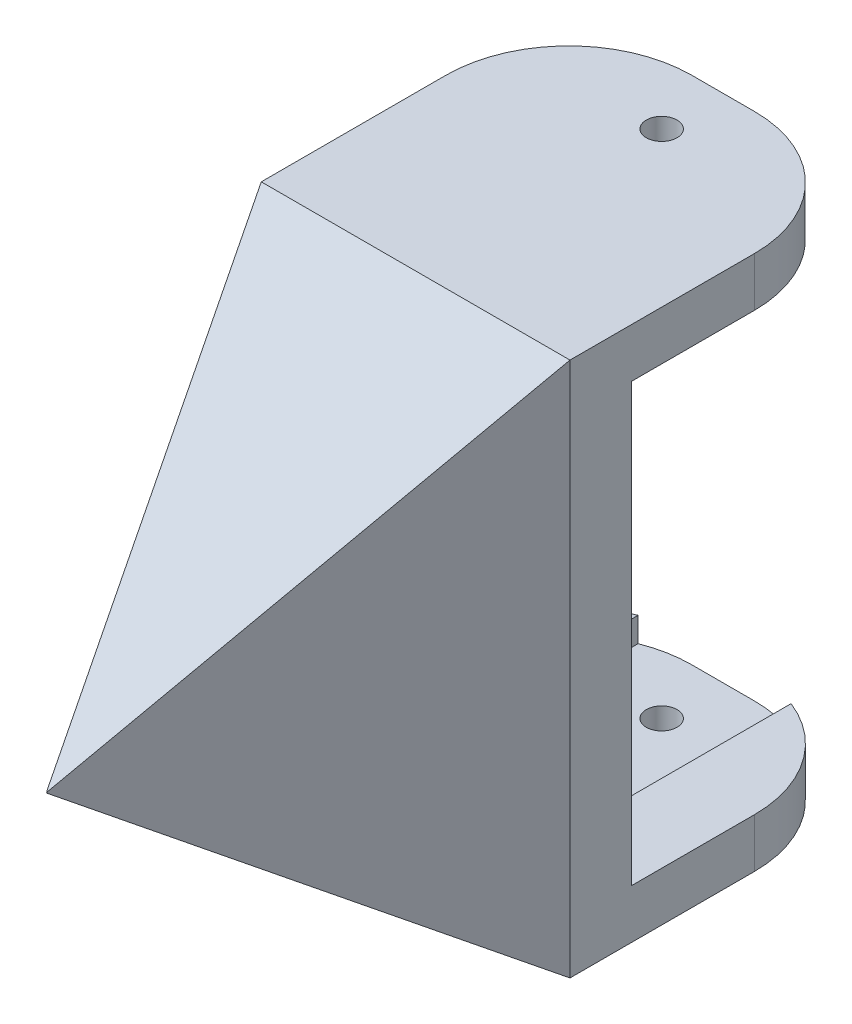
SolidWorks part; units mm, degrees
ref_plane "Front Plane" through (0, 0, 0) normal (0, 0, 1) x (1, 0, 0)
ref_plane "Top Plane" through (0, 0, 0) normal (0, 1, 0) x (1, 0, 0)
ref_plane "Right Plane" through (0, 0, 0) normal (1, 0, 0) x (0, 0, -1)
sketch "Sketch4" plane through (0, 0, 0) normal (0, 0, 1) x (1, 0, 0)
  line L1 (-6.23, -9.975) -> (6.23, -9.975)
  line L2 (-6.23, -9.975) -> (-6.23, 7.275)
  line L3 (-6.23, 7.275) -> (6.23, 7.275)
  line L4 (6.23, -9.975) -> (6.23, 7.275)
  point P4 (0, 7.275)
  dimension "D1" = 12.46
  dimension "D2" = 17.25
  dimension "D3" = 9.975
extrude "Boss-Extrude3" add sketch "Sketch4" along normal blind 6
sketch "Sketch8" plane through (0, -9.975, 0) normal (0, -1, 0) x (-1, 0, 0)
  circle A0 centre (0, -23.55) radius 12.5468
  circle A1 centre (0, -23.55) radius 11.15
  dimension "D1" = 22.3
  dimension "D2" = 23.55
extrude "Boss-Extrude6" add sketch "Sketch8" along normal blind 7.3 and the other way up to surface (17.25 mm away) other way up to face at (0, 7.275, 3)
sketch "Sketch5" plane through (0, 7.275, 0) normal (0, 1, 0) x (1, 0, 0)
  line L8 (12.5468, -23.55) -> (12.5468, 0)
  line L9 (12.5468, 0) -> (6.23, 0)
  line L10 (-12.5468, -23.55) -> (-12.5468, 0)
  line L11 (-12.5468, 0) -> (-6.23, 0)
  line L12 (-6.23, 0) -> (-6.23, -29.7)
  line L14 (6.23, -29.7) -> (6.23, 0)
  line L15 (-6.23, -29.7) -> (6.23, -29.7)
  line L16 (6.23, -6) -> (-6.23, -6) construction
  circle A0 centre (0, -23.55) radius 12.5468 construction
  arc A1 (-12.5468, -23.55) -> (12.5468, -23.55) centre (0, -23.55) ccw
  dimension "D1" = 23.7
  dimension "D2" = 23.55
extrude "Boss-Extrude4" add sketch "Sketch5" against normal up to surface (17.25 mm away) up to face at (0, -9.975, 3)
sketch "Sketch6" plane through (0, 7.275, 0) normal (0, 1, 0) x (1, 0, 0)
  line L0 (6.23, -6) -> (-6.23, -6) construction
  line L3 (6.23, -29.7) -> (-6.23, -29.7) construction
  circle A0 centre (0, -3.5) radius 2
  circle A1 centre (0, -32.2) radius 2
  dimension "D1" = 4
  dimension "D3" = 4
  dimension "D2" = 2.5
  dimension "D4" = 2.5
extrude "Cut-Extrude1" cut sketch "Sketch6" against normal blind 5
chamfer "Chamfer1" distance 0.5 angle 60 2 edges at (0, 7.275, 5.5) (0, 7.275, 34.2) first distance on face at (0, 7.275, 5.5)
sketch "Sketch10" plane through (0, 7.275, 0) normal (0, 1, 0) x (1, 0, 0)
  line L1 (-6.23, -6) -> (6.23, -6)
  line L2 (-6.23, -6) -> (-6.23, -29.7)
  line L3 (-6.23, -29.7) -> (6.23, -29.7)
  line L4 (6.23, -6) -> (6.23, -29.7)
extrude "Cut-Extrude3" cut sketch "Sketch10" against normal up to surface (17.25 mm away) up to face at (0, -9.975, 10.3399)
ref_plane "Plane1" through (0, 0, 36.0968) normal (0, 0, 1) x (1, 0, 0)
sketch "Sketch11" plane through (0, 0, 36.0968) normal (0, 0, 1) x (1, 0, 0)
  line L0 (-11.15, -9.975) -> (11.15, -9.975) construction
  line L1 (-2.5, -6.975) -> (2.5, -6.975)
  line L2 (-2.5, -6.975) -> (-2.5, -9.975)
  line L3 (-2.5, -9.975) -> (2.5, -9.975)
  line L4 (2.5, -6.975) -> (2.5, -9.975)
  point P4 (0, -6.975)
  dimension "D1" = 0
  dimension "D2" = 5
  dimension "D3" = 3
extrude "Cut-Extrude4" cut sketch "Sketch11" against normal up to next
sketch "Sketch13" plane through (0, -17.275, 0) normal (0, -1, 0) x (1, 0, 0)
  line L0 (-12.5468, 23.55) -> (-12.5468, 0)
  line L1 (-12.5468, 0) -> (12.5468, 0)
  line L2 (12.5468, 0) -> (12.5468, 23.55)
  arc A0 (-12.5468, 23.55) -> (12.5468, 23.55) centre (0, 23.55) ccw
  point P3 (0, 0)
extrude "Boss-Extrude7" add sketch "Sketch13" against normal up to surface (7.3 mm away) up to face at (0, -9.975, 10.3399)
sketch "Sketch15" plane through (0, 7.275, 0) normal (0, 1, 0) x (1, 0, 0)
  line L0 (-12.5468, 0) -> (12.5468, 0)
  line L1 (12.5468, 0) -> (12.5468, -23.55)
  line L2 (-12.5468, 0) -> (-12.5468, -23.55)
  line L3 (6.23, -6) -> (6.23, -29.7) construction
  line L4 (-6.23, -0.8) -> (6.23, -0.8)
  line L5 (-6.23, -0.8) -> (-6.23, -33.5)
  line L6 (-5.23, -34.5) -> (5.23, -34.5)
  line L7 (6.23, -0.8) -> (6.23, -33.5)
  arc A0 (-12.5468, -23.55) -> (12.5468, -23.55) centre (0, -23.55) ccw
  circle A1 centre (0, -3.5) radius 2 construction
  arc A2 (5.23, -34.5) -> (6.23, -33.5) centre (5.23, -33.5) ccw
  arc A3 (-6.23, -33.5) -> (-5.23, -34.5) centre (-5.23, -33.5) ccw
  point P15 (0, -0.8)
  dimension "D1" = 0.8
  dimension "D3" = 1
  dimension "D2" = 2.7
  dimension "D4" = 0
  dimension "D5" = 34.5
extrude "Boss-Extrude9" add sketch "Sketch15" along normal blind 10
sketch "Sketch17" plane through (-12.5468, 4.7282, 0) normal (1, 0, 0) x (0, -1, 0)
  line L0 (26.4782, 25) -> (26.4782, 0)
  line L1 (26.4782, 0) -> (-17.0218, 0)
  line L2 (-17.0218, 0) -> (-17.0218, 25)
  line L3 (-17.0218, 25) -> (-13.0218, 25)
  line L4 (-13.0218, 25) -> (-13.0218, 5)
  line L5 (-13.0218, 5) -> (22.4782, 5)
  line L6 (22.4782, 5) -> (22.4782, 25)
  line L7 (22.4782, 25) -> (26.4782, 25)
  point P2 (4.7282, 5)
  point P10 (4.7282, 0)
  dimension "D1" = 4
  dimension "D2" = 35.5
  dimension "D3" = 0
  dimension "D4" = 25
  dimension "D5" = 5
extrude "Boss-Extrude10" add sketch "Sketch17" along normal up to surface (25.0936 mm away) up to face at (12.5468, 0, 11.775)
sketch "Sketch18" plane through (0, -17.75, 0) normal (0, 1, 0) x (0, 0, 1)
  line L0 (-25, -12.5468) -> (-25, 12.5468) construction
  line L1 (-25, 6.2191) -> (-5, 6.2191)
  line L2 (-25, 6.2191) -> (-25, -6.2191)
  line L3 (-25, -6.2191) -> (-5, -6.2191)
  line L4 (-5, 6.2191) -> (-5, -6.2191)
  line L5 (-5, -12.5468) -> (-5, 12.5468) construction
  point P6 (-25, 0)
  point P7 (-25, 0)
  dimension "D1" = 0
extrude "Cut-Extrude5" cut sketch "Sketch18" against normal blind 2
sketch "Sketch19" plane through (0, -19.75, 0) normal (0, 1, 0) x (0, 0, 1)
  line L0 (-25, -12.5468) -> (-25, 12.5468) construction
  circle A0 centre (-20, 0) radius 1.25
  dimension "D1" = 2.5
  dimension "D2" = 5
extrude "Cut-Extrude6" cut sketch "Sketch19" against normal through all both and the other way through all
fillet "Fillet1" radius 10 4 edges at (12.5468, -19.75, -25) (-12.5468, -19.75, -25) (-12.5468, 19.75, -25) (12.5468, 19.75, -25)
ref_plane "Plane2" through (0, 0, 0) normal (1, 0, 0) x (0, 0, -1)
ref_plane "Plane3" through (0, 0, 0) normal (0, -1, 0) x (-1, 0, 0)
sketch "Sketch20" plane through (0, 17.275, 0) normal (0, 1, 0) x (1, 0, 0)
  line L1 (12.5468, 0) -> (-12.5468, 0)
  line L2 (12.5468, 0) -> (12.5468, -36.0968)
  line L3 (12.5468, -36.0968) -> (-12.5468, -36.0968)
  line L4 (-12.5468, 0) -> (-12.5468, -36.0968)
extrude "Cut-Extrude7" cut sketch "Sketch20" against normal through all both and the other way through all
sketch "Sketch21" plane through (0, 21.75, 0) normal (0, 1, 0) x (1, 0, 0)
  line L0 (12.5468, 0) -> (-0.0254, -30)
  line L1 (-0.0254, -30) -> (-12.5468, 0)
  line L2 (-12.5468, 0) -> (12.5468, 0)
  dimension "D1" = 30
extrude "Boss-Extrude11" add sketch "Sketch21" against normal up to vertex (43.5 mm away) up to point (-12.5468, -21.75, 0)
sketch "Sketch22" plane through (0, 0, 0) normal (1, 0, 0) x (0, 0, -1)
  line L13 (0, 21.75) -> (-30, 0.01)
  line L14 (-30, -21.75) -> (-30, 21.75) construction
  line L15 (-30, 0.01) -> (-30, 21.75)
  line L16 (-30, 21.75) -> (0, 21.75)
  line L17 (0, -21.75) -> (-30, -21.75)
  line L18 (-30, -21.75) -> (-30, -0.01)
  line L19 (-30, -0.01) -> (0, -21.75)
  dimension "D1" = 0.02
  dimension "D2" = 0.01
extrude "Cut-Extrude8" cut sketch "Sketch22" against normal through all both and the other way through all
sketch "Sketch23" plane through (0, 0, 0) normal (0, 0, -1) x (-1, 0, 0)
  line L0 (12.5468, 17.75) -> (0, 0)
  line L1 (0, 0) -> (12.5468, -21.75)
  line L2 (12.5468, -21.75) -> (12.5468, 17.75)
extrude "Cut-Extrude9" cut sketch "Sketch23" against normal through all both and the other way through all
